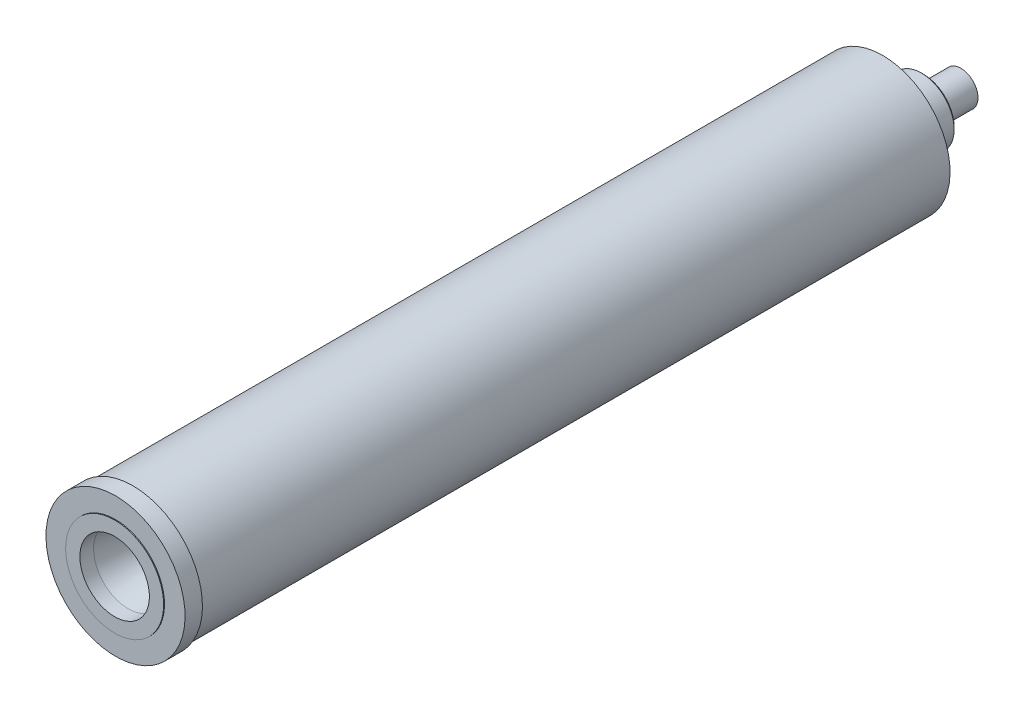
SolidWorks part; units mm, degrees
material "6061-T6 (SS)"
ref_plane "Front Plane" through (0, 0, 0) normal (0, 0, 1) x (1, 0, 0)
ref_plane "Top Plane" through (0, 0, 0) normal (0, 1, 0) x (1, 0, 0)
ref_plane "Right Plane" through (0, 0, 0) normal (1, 0, 0) x (0, 0, -1)
sketch "Sketch1" plane through (0, 0, 0) normal (1, 0, 0) x (0, 0, -1)
  line L0 (-266.5566, 50.8) -> (-253.8566, 50.8)
  line L1 (-253.8566, 50.8) -> (-253.8566, 49.2125)
  line L2 (-253.8566, 49.2125) -> (293.878, 49.2125)
  line L3 (293.878, 49.2125) -> (293.878, 23.876)
  line L4 (271.028, 0) -> (351.028, 0)
  line L5 (271.028, 0) -> (271.028, 29.25)
  line L6 (271.028, 29.25) -> (-147.1916, 29.25)
  line L7 (-147.1916, 29.25) -> (-147.1916, 40.25)
  line L8 (-147.1916, 40.25) -> (-155.1855, 40.25)
  line L9 (-155.1855, 40.25) -> (-182.1916, 13.2438)
  line L10 (-197.1916, 14.8204) -> (-182.1916, 13.2438)
  line L11 (-197.1916, 14.8204) -> (-257.1916, 25.4)
  line L12 (-257.1916, 25.4) -> (-267.1916, 25.4)
  line L13 (-266.5566, 50.8) -> (-266.5566, 35.8)
  line L14 (473.12, 0) -> (-433.5179, 0) construction
  line L15 (293.878, 23.876) -> (323.723, 23.876)
  line L16 (323.723, 23.876) -> (323.723, 12.5)
  line L17 (323.723, 12.5) -> (351.028, 12.5)
  line L18 (351.028, 12.5) -> (351.028, 0)
  line L19 (-266.5566, 35.8) -> (-267.1916, 35.8)
  line L20 (-267.1916, 35.8) -> (-267.1916, 25.4)
  point P1 (323.723, 18.188)
  point P25 (351.028, 6.25)
  dimension "D2" = 547.7346
  dimension "D3" = 49.2125
  dimension "D4" = 6
  dimension "D5" = 10
  dimension "D6" = 60
  dimension "D7" = 57.15
  dimension "D8" = 29.845
  dimension "D9" = 135
  dimension "D10" = 23.876
  dimension "D11" = 12.5
  dimension "D12" = 12.7
  dimension "D13" = 35
  dimension "D14" = 15
  dimension "D15" = 10
  dimension "D16" = 50.8
  dimension "D17" = 25.4
  dimension "D18" = 0.635
  dimension "D19" = 15
  dimension "D20" = 29.25
  dimension "D21" = 351.028
  dimension "D22" = 11
  dimension "D23" = 80
revolve "Revolve1" add sketch "Sketch1" angle 360 about L14
chamfer "Chamfer1" distance 1.5 angle 45 1 edges at (0, 23.876, -323.723)
hole_wizard "3/8-16 Tapped Hole1" positions "Sketch2" profile "Sketch4" tap size "3/8-16" standard "ANSI Inch"
sketch "Sketch2" plane through (0, 0, -351.028) normal (0, 0, -1) x (-1, 0, 0)
  point P0 (0, 0)
sketch "Sketch4" plane through (0, 0, -351.028) normal (1, 0, 0) x (0, 1, 0)
  line L0 (0, 0) -> (0, 27.7847)
  line L1 (0, 27.7847) -> (3.9687, 25.4)
  line L2 (3.9687, 25.4) -> (3.9687, 1.1989)
  line L3 (3.9687, 1.1989) -> (5.3975, 0)
  line L5 (5.3975, 0) -> (0, 0)
  line L6 (-3.9687, 1.1989) -> (-5.3975, 0) construction
  line L10 (0, 27.7847) -> (-3.9688, 25.4) construction
  line L11 (0, -6.35) -> (0, 107.95) construction
  dimension "Tap Drill Dia." = 7.9375
  dimension "Tap Drill Depth" = 25.4
  dimension "Near C'Sink Dia." = 10.795
  dimension "Near C'Sink Angle" = 100
  dimension "Drill Angle" = 118
cosmetic thread "Hole Thread1" parameters "D1"=19.05, "D2"=9.525
